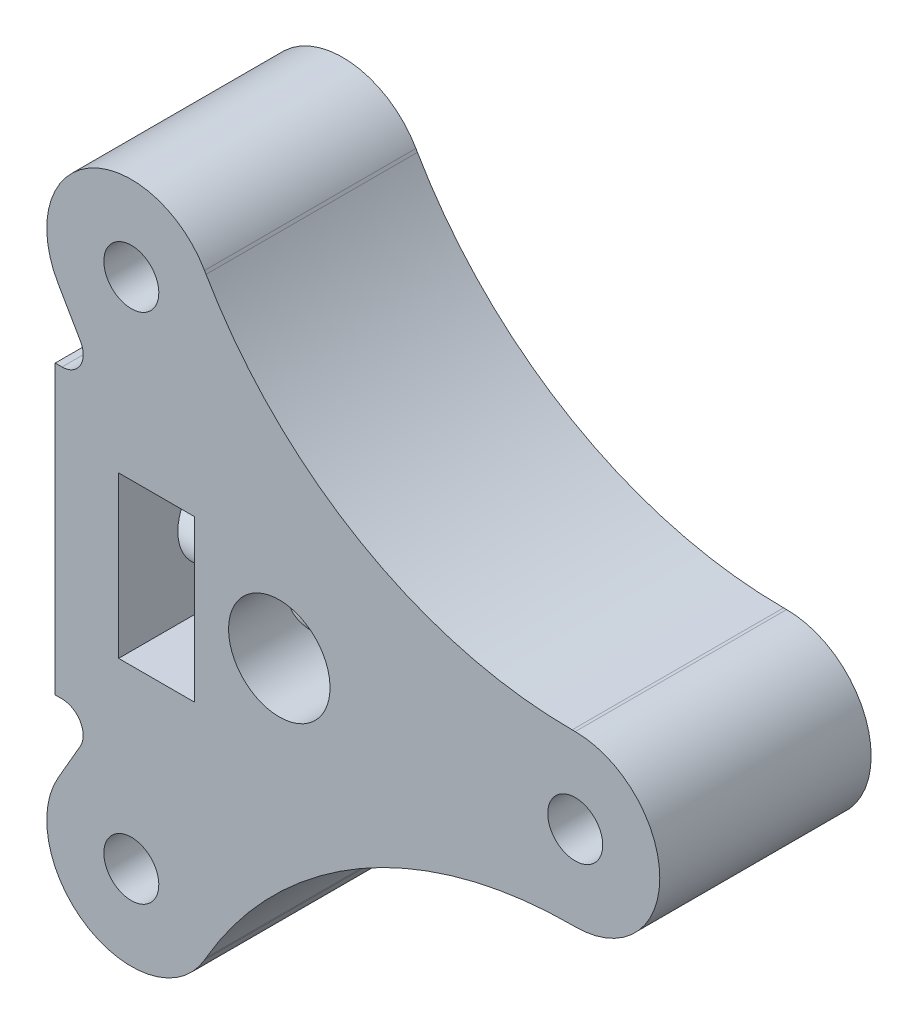
SolidWorks part; units mm, degrees
material "ABS PC"
ref_plane "Front Plane" through (0, 0, 0) normal (0, 0, 1) x (1, 0, 0)
ref_plane "Top Plane" through (0, 0, 0) normal (0, 1, 0) x (1, 0, 0)
ref_plane "Right Plane" through (0, 0, 0) normal (1, 0, 0) x (0, 0, -1)
other "Center of Mass"
sketch "Sketch1" plane through (0, 0, 0) normal (0, 0, 1) x (1, 0, 0)
  line L0 (-13.462, 8.636) -> (-1.27, 8.636)
  line L1 (-9.652, 4.826) -> (-5.08, 4.826)
  line L2 (-9.652, 4.826) -> (-9.652, -4.826)
  line L3 (-9.652, -4.826) -> (-5.08, -4.826)
  line L4 (-5.08, 4.826) -> (-5.08, -4.826)
  line L6 (-13.462, -8.636) -> (-1.27, -8.636)
  line L7 (-13.462, 8.636) -> (-13.462, -8.636)
  line L8 (-1.27, 8.636) -> (3.7294, 4.3304)
  line L9 (-1.27, -8.636) -> (3.7294, -4.3304)
  line L10 (-1.27, 8.636) -> (-1.27, -8.636) construction
  circle A0 centre (0, 0) radius 3.048
  arc A1 (3.7294, -4.3304) -> (3.7294, 4.3304) centre (0, 0) ccw
  dimension "D1" = 6.096
  dimension "D2" = 11.43
  dimension "D6" = 5.08
  dimension "D3" = 9.652
  dimension "D4" = 4.572
  dimension "D5" = 4.826
  dimension "D7" = 3.81
extrude "Boss-Extrude1" add sketch "Sketch1" along normal blind 17.78
sketch "Sketch4" plane through (0, 0, 0) normal (0, 0, -1) x (-1, 0, 0)
  circle A0 centre (0, 0) radius 28.575 construction
  dimension "D1" = 57.15
sketch "Sketch3" plane through (-5.08, 0, 0) normal (-1, 0, 0) x (0, 0, 1)
  line L0 (17.78, 4.826) -> (0, 4.826) construction
  line L1 (3.937, -4.826) -> (13.843, -4.826)
  line L2 (3.937, -4.826) -> (3.937, 4.826)
  line L3 (3.937, 4.826) -> (13.843, 4.826)
  line L4 (13.843, -4.826) -> (13.843, 4.826)
  line L5 (3.937, -4.826) -> (13.843, 4.826) construction
  line L6 (3.937, 4.826) -> (13.843, -4.826) construction
  line L8 (3.937, 4.826) -> (0, 4.826)
  line L9 (3.937, 4.826) -> (3.937, -4.826)
  line L10 (3.937, -4.826) -> (0, -4.826)
  line L11 (0, 4.826) -> (0, -4.826)
  point P0 (8.89, 0)
  line M4 (0, 4.826) -> (0, -4.826)
  line M5 (0, -4.826) -> (17.78, -4.826)
  line M7 (17.78, 4.826) -> (0, 4.826)
  dimension "D1" = 9.906
extrude "Boss-Extrude2" add sketch "Sketch3" along normal up to surface (4.572 mm away) contours L2 M5 M7 M4 region at (-5.08, 0, 1.9685) up to face at (-9.652, 0, 8.89)
sketch "Sketch5" plane through (0, 0, 0) normal (0, 0, -1) x (-1, 0, 0)
  line L0 (0, 0) -> (8.89, 15.3979) construction
  line L1 (-2.9329, 5.08) -> (4.4906, 17.9379)
  line L2 (8.6522, 4.826) -> (13.2894, 12.8579)
  line L3 (-2.9329, -5.08) -> (4.4906, -17.9379)
  line L4 (8.6522, -4.826) -> (13.2894, -12.8579)
  line L5 (0, 0) -> (8.89, -15.3979) construction
  line L6 (-2.9329, 5.08) -> (-17.78, 5.08)
  line L7 (-2.9329, -5.08) -> (-17.78, -5.08)
  line L8 (0, 0) -> (-17.78, 0) construction
  line L9 (0, 0) -> (-28.575, 0) construction
  line L11 (8.6522, 4.826) -> (5.08, 4.826)
  line L13 (8.6522, -4.826) -> (5.08, -4.826)
  line L14 (5.08, 4.826) -> (5.08, -4.826)
  arc A1 (13.2894, 12.8579) -> (4.4906, 17.9379) centre (8.89, 15.3979) ccw
  circle A2 centre (8.89, 15.3979) radius 1.651
  arc A4 (4.4906, -17.9379) -> (13.2894, -12.8579) centre (8.89, -15.3979) ccw
  circle A5 centre (8.89, -15.3979) radius 1.651
  arc A7 (-17.78, 5.08) -> (-17.78, -5.08) centre (-17.78, 0) ccw
  circle A8 centre (-17.78, 0) radius 1.651
  circle A9 centre (0, 0) radius 28.575 construction
  circle A12 centre (0, 0) radius 3.048
  point P3 (4.445, 7.699)
  point P13 (4.445, -7.699)
  point P21 (-8.89, 0)
  point P28 (0, 0)
  dimension "D2" = 5.08
  dimension "D3" = 3.302
  dimension "D1" = 17.78
  dimension "D5" = 0
  dimension "D4" = 3
extrude "Boss-Extrude3" add sketch "Sketch5" against normal blind 17.78
fillet "Fillet1" radius 25.4 2 edges at (2.9329, -5.08, 8.89) (2.9329, 5.08, 8.89)
fillet "Fillet2" radius 1.27 2 edges at (-10.8519, 8.636, 8.89) (-10.8519, -8.636, 8.89)
sketch "Sketch2" plane through (-13.462, 0, 0) normal (-1, 0, 0) x (0, 0, 1)
  line L0 (0, 0) -> (17.78, 0) construction
  line L1 (0, 8.636) -> (0, -8.636) construction
  line L2 (17.78, 8.636) -> (17.78, -8.636) construction
  circle A0 centre (8.89, 0) radius 2.794
  dimension "D1" = 5.588
extrude "Cut-Extrude2" cut sketch "Sketch2" against normal blind 12.7
sketch "Sketch7" plane through (-13.462, 0, 0) normal (-1, 0, 0) x (0, 0, 1)
  line L1 (2.54, -25.4) -> (15.24, -25.4)
  line L2 (2.54, -25.4) -> (2.54, 25.4)
  line L3 (2.54, 25.4) -> (15.24, 25.4)
  line L4 (15.24, -25.4) -> (15.24, 25.4)
  line L5 (2.54, -25.4) -> (15.24, 25.4) construction
  line L6 (2.54, 25.4) -> (15.24, -25.4) construction
  line L7 (-3.1594, -31.9325) -> (20.9394, -31.9325)
  line L8 (-3.1594, -31.9325) -> (-3.1594, 31.9325)
  line L9 (-3.1594, 31.9325) -> (20.9394, 31.9325)
  line L10 (20.9394, -31.9325) -> (20.9394, 31.9325)
  line L11 (-3.1594, -31.9325) -> (20.9394, 31.9325) construction
  line L12 (-3.1594, 31.9325) -> (20.9394, -31.9325) construction
  point P0 (8.89, 0)
  point P6 (8.89, 0)
  dimension "D1" = 12.7
  dimension "D2" = 50.8
extrude "Cut-Extrude3" cut sketch "Sketch7" against normal through all both and the other way through all
